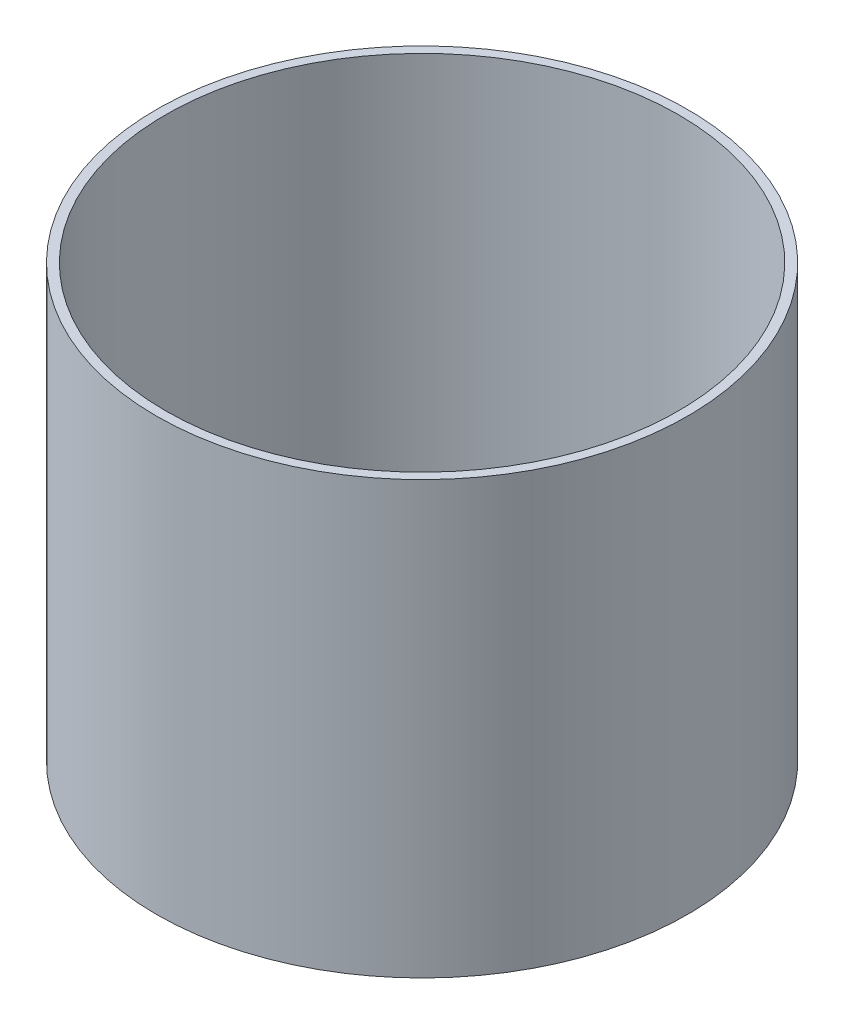
SolidWorks part; units mm, degrees
material "AISI 304"
ref_plane "Front" through (0, 0, 0) normal (0, 0, 1) x (1, 0, 0)
ref_plane "Top" through (0, 0, 0) normal (0, 1, 0) x (1, 0, 0)
ref_plane "Right" through (0, 0, 0) normal (1, 0, 0) x (0, 0, -1)
sketch "Sketch1" plane through (0, 0, 0) normal (0, 1, 0) x (1, 0, 0)
  circle A0 centre (0, 0) radius 109.5375
  circle A1 centre (0, 0) radius 105.7783
  dimension "D1" = 219.075
  dimension "D2" = 3.7592
extrude "Boss-Extrude1" add sketch "Sketch1" along normal mid plane 178
